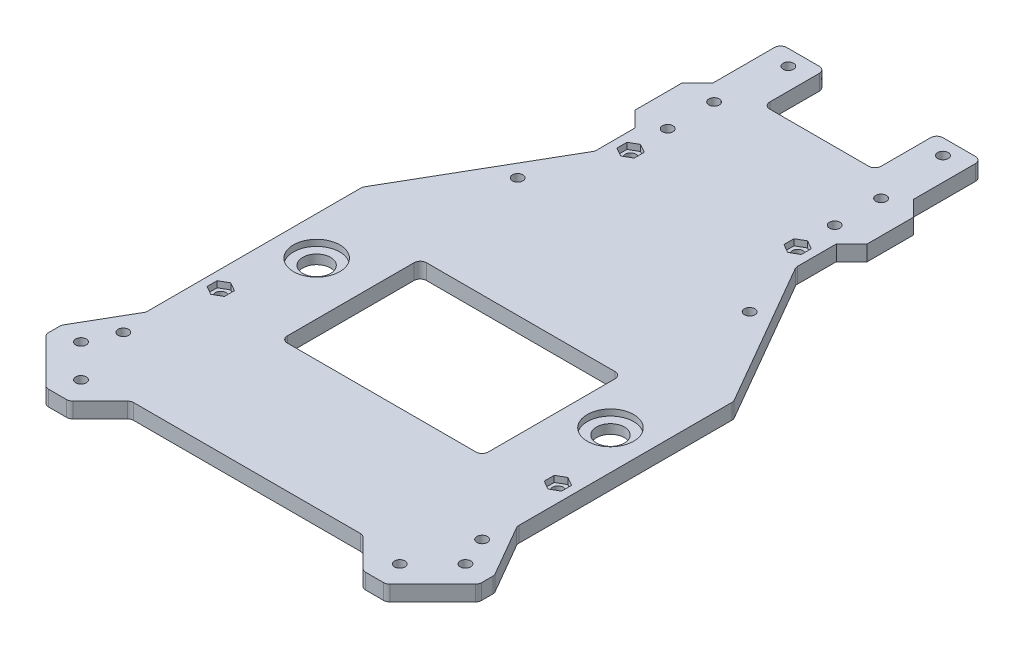
SolidWorks part; units mm, degrees
material "ABS PC"
ref_plane "Front Plane" through (0, 0, 0) normal (0, 0, 1) x (1, 0, 0)
ref_plane "Top Plane" through (0, 0, 0) normal (0, 1, 0) x (1, 0, 0)
ref_plane "Right Plane" through (0, 0, 0) normal (1, 0, 0) x (0, 0, -1)
sketch "Sketch1" plane through (0, 0, 0) normal (0, 1, 0) x (1, 0, 0)
  line L1 (70, -110) -> (-70, -110)
  line L2 (70, -110) -> (70, 110)
  line L3 (70, 110) -> (-70, 110)
  line L4 (-70, -110) -> (-70, 110)
  line L5 (70, -110) -> (-70, 110) construction
  line L6 (70, 110) -> (-70, -110) construction
  point P0 (0, 0)
  dimension "D1" = 220
  dimension "D2" = 140
extrude "Boss-Extrude1" add sketch "Sketch1" along normal blind 5
sketch "Sketch8" plane through (0, 5, 0) normal (0, 1, 0) x (1, 0, 0)
  line L0 (-70, 110) -> (-32.5, 110)
  line L1 (70, 110) -> (-70, 110) construction
  line L2 (-32.5, 110) -> (-32.5, 44.9519)
  line L3 (-32.5, 44.9519) -> (-70, -20)
  line L4 (-70, 110) -> (-70, -110) construction
  line L5 (-70, 110) -> (-70, -20)
  line L6 (0, 110) -> (0, -110) construction
  line L7 (-70, -110) -> (70, -110) construction
  line L8 (70, 110) -> (70, -20)
  line L9 (32.5, 44.9519) -> (70, -20)
  line L10 (32.5, 110) -> (32.5, 44.9519)
  line L11 (70, 110) -> (32.5, 110)
  dimension "D1" = 130
  dimension "D2" = 30
  dimension "D3" = 65
extrude "Cut-Extrude1" cut sketch "Sketch8" against normal blind 5
chamfer "Chamfer3" distance 15 angle 45 2 edges at (70, 2.5, 110) (-70, 2.5, 110)
sketch "Sketch10" plane through (0, 0, 0) normal (0, 1, 0) x (1, 0, 0)
  line L0 (0, 110) -> (0, -110) construction
  line L1 (32.5, 110) -> (-32.5, 110) construction
  line L2 (-55, -110) -> (55, -110) construction
  line L3 (-27, 78) -> (-27, 63) construction
  line L4 (-62.5, -102.5) -> (-56.8431, -96.8431) construction
  line L5 (-62.1464, -91.5398) -> (-51.5398, -102.1464) construction
  line L6 (-70, -95) -> (-55, -110) construction
  point P9 (27, 63)
  point P10 (27, 78)
  point P17 (51.5398, -102.1464)
  point P18 (62.1464, -91.5398)
  dimension "D1" = 15
  dimension "D2" = 27
  dimension "D3" = 32
  dimension "D4" = 15
  dimension "D5" = 8
sketch "Sketch15" plane through (0, 5, 0) normal (0, 1, 0) x (1, 0, 0)
  line L0 (0, 110) -> (0, -110) construction
  line L1 (32.5, 110) -> (-32.5, 110) construction
  line L2 (-55, -110) -> (55, -110) construction
  line L3 (25, 100) -> (-25, 100) construction
  line L4 (37.5, 25) -> (-37.5, 25) construction
  line L5 (58, -57) -> (-58, -57) construction
  point P9 (0, 100)
  point P13 (0, 25)
  point P15 (0, -57)
  dimension "D1" = 50
  dimension "D2" = 10
  dimension "D3" = 75
  dimension "D4" = 85
  dimension "D5" = 116
  dimension "D6" = 167
hole_wizard "CSK for M3 Flat Head Machine Screw3" positions "Sketch16" profile "Sketch17" countersink size "M3" standard "ANSI Metric"
sketch "Sketch16" plane through (0, 0, 0) normal (0, 1, 0) x (1, 0, 0)
  point P6 (37.5, 25)
  point P9 (-37.5, 25)
  point P12 (-25, 100)
  point P15 (25, 100)
sketch "Sketch17" plane through (37.5, 0, -25) normal (1, 0, 0) x (0, 0, -1)
  line L0 (0, 0) -> (0, 6.0215)
  line L1 (0, 6.0215) -> (1.7, 5)
  line L2 (1.7, 5) -> (1.7, 1.45)
  line L3 (1.7, 1.45) -> (3.15, 0)
  line L5 (3.15, 0) -> (0, 0)
  line L6 (-1.7, 1.45) -> (-3.15, 0) construction
  line L10 (0, 6.0215) -> (-1.7, 5) construction
  line L11 (0, -6.35) -> (0, 107.95) construction
  dimension "Hole Dia." = 3.4
  dimension "Hole Depth" = 5
  dimension "Near C'Sink Dia." = 6.3
  dimension "Near C'Sink Angle" = 90
  dimension "Drill Angle" = 118
sketch "Sketch18" plane through (0, 5, 0) normal (0, 1, 0) x (1, 0, 0)
  line L0 (32.5, 110) -> (-32.5, 110) construction
  line L1 (-46.4338, 114.6286) -> (34.8035, 114.6286)
  line L2 (-46.4338, 114.6286) -> (-46.4338, 105)
  line L3 (-46.4338, 105) -> (34.8035, 105)
  line L4 (34.8035, 114.6286) -> (34.8035, 105)
  dimension "D1" = 5
extrude "Cut-Extrude2" cut sketch "Sketch18" against normal blind 5
sketch "Sketch34" plane through (0, 5, 0) normal (0, 1, 0) x (1, 0, 0)
  line L0 (-70, -20) -> (-60, -2.6795)
  line L1 (-70, -20) -> (-32.5, 44.9519) construction
  line L2 (-60, -2.6795) -> (-60, -72.6795)
  line L3 (-60, -72.6795) -> (-70, -90)
  line L4 (-70, -20) -> (-70, -95) construction
  line L5 (-70, -90) -> (-70, -20)
  line L6 (0, -90.4055) -> (0, -61.6307) construction
  line L7 (70, -90) -> (70, -20)
  line L8 (60, -72.6795) -> (70, -90)
  line L9 (60, -2.6795) -> (60, -72.6795)
  line L10 (70, -20) -> (60, -2.6795)
  line L11 (-55, -110) -> (55, -110) construction
  dimension "D1" = 120
  dimension "D2" = 20
extrude "Cut-Extrude8" cut sketch "Sketch34" against normal blind 10
chamfer "Chamfer4" [suppressed] distance 20 angle 30
sketch "Sketch35" plane through (0, 5, 0) normal (0, 1, 0) x (1, 0, 0)
  line L1 (-30.5, -58.5) -> (34.5, -58.5)
  line L2 (-30.5, -58.5) -> (-30.5, -13.5)
  line L3 (-30.5, -13.5) -> (34.5, -13.5)
  line L4 (34.5, -58.5) -> (34.5, -13.5)
  line L5 (-30.5, -58.5) -> (34.5, -13.5) construction
  line L6 (-30.5, -13.5) -> (34.5, -58.5) construction
  point P0 (2, -36)
  dimension "D1" = 2
  dimension "D2" = 65
  dimension "D3" = 45
  dimension "D4" = 36
extrude "Cut-Extrude9" cut sketch "Sketch35" against normal through all
fillet "Fillet1" radius 2 4 edges at (-30.5, 2.5, 58.5) (-30.5, 2.5, 13.5) (34.5, 2.5, 13.5) (34.5, 2.5, 58.5)
sketch "Sketch36" plane through (0, 5, 0) normal (0, 1, 0) x (1, 0, 0)
  line L0 (0, -110) -> (0, -100) construction
  line L1 (-55, -110) -> (55, -110) construction
  line L2 (-47.5, -110) -> (-37.5, -100)
  line L3 (-37.5, -100) -> (37.5, -100)
  line L4 (-47.5, -110) -> (47.5, -110)
  line L6 (-70, -95) -> (-55, -110) construction
  line L7 (47.5, -110) -> (37.5, -100)
  dimension "D1" = 10
  dimension "D2" = 95
extrude "Cut-Extrude10" cut sketch "Sketch36" against normal through all
sketch "Sketch38" plane through (0, 0, 0) normal (0, -1, 0) x (1, 0, 0)
  line L0 (0, -105) -> (0, -90) construction
  line L1 (-32.5, -105) -> (32.5, -105) construction
  line L2 (18, -85) -> (-18, -85)
  line L3 (-18, -85) -> (-18, -105)
  line L4 (-18, -105) -> (18, -105)
  line L5 (18, -85) -> (18, -105)
  dimension "D1" = 90
  dimension "D2" = 20
  dimension "D3" = 36
extrude "Cut-Extrude14" cut sketch "Sketch38" against normal through all
sketch "Sketch39" plane through (0, 0, 0) normal (0, -1, 0) x (1, 0, 0)
  line L0 (0, 37.973) -> (0, 15.9654) construction
  circle A0 centre (-47.5, 30) radius 4.5
  circle A1 centre (47.5, 30) radius 4.5
  dimension "D1" = 95
  dimension "D2" = 9
  dimension "D3" = 30
extrude "Cut-Extrude15" cut sketch "Sketch39" against normal through all
hole_wizard "CSK for M3 Flat Head Machine Screw2" positions "Sketch40" profile "Sketch41" countersink size "M3" standard "ANSI Metric"
sketch "Sketch40" plane through (0, 0, 0) normal (0, -1, 0) x (-1, 0, 0)
  point P0 (-58, -82)
  point P3 (58, -82)
sketch "Sketch41" plane through (58, 0, 82) normal (1, 0, 0) x (0, 0, -1)
  line L0 (0, 0) -> (0, 11.0215)
  line L1 (0, 11.0215) -> (1.7, 10)
  line L2 (1.7, 10) -> (1.7, 1.45)
  line L3 (1.7, 1.45) -> (3.15, 0)
  line L5 (3.15, 0) -> (0, 0)
  line L6 (-1.7, 1.45) -> (-3.15, 0) construction
  line L10 (0, 11.0215) -> (-1.7, 10) construction
  line L11 (0, -6.35) -> (0, 107.95) construction
  dimension "Hole Dia." = 3.4
  dimension "Hole Depth" = 10
  dimension "Near C'Sink Dia." = 6.3
  dimension "Near C'Sink Angle" = 90
  dimension "Drill Angle" = 118
hole_wizard "Ø3.5 (3.5) Diameter Hole1" positions "Sketch45" profile "Sketch46" hole size "Ø3.5" standard "ANSI Metric"
sketch "Sketch45" plane through (0, 5, 0) normal (0, 1, 0) x (1, 0, 0)
  line L0 (-32.5, 44.9519) -> (-32.5, 105) construction
  line L1 (-60, -72.6795) -> (-60, -2.6795) construction
  line L2 (-32.5, 105) -> (-18, 105) construction
  point P0 (-54.5, -54)
  point P2 (-27, 51)
  dimension "D1" = 5.5
  dimension "D2" = 5.5
  dimension "D3" = 54
  dimension "D4" = 105
sketch "Sketch46" plane through (-54.5, 5, 54) normal (1, 0, 0) x (0, 0, 1)
  line L0 (0, 0) -> (0, 6.0515)
  line L1 (0, 6.0515) -> (1.75, 5)
  line L2 (1.75, 5) -> (1.75, 0)
  line L5 (1.75, 0) -> (0, 0)
  line L10 (0, 6.0515) -> (-1.75, 5) construction
  line L11 (0, -6.35) -> (0, 107.95) construction
  dimension "Hole Dia." = 3.5
  dimension "Hole Depth" = 5
  dimension "Drill Angle" = 118
mirror "Mirror1" about plane through (0, 0, 0) normal (1, 0, 0) of "Ø3.5 (3.5) Diameter Hole1"
sketch "Sketch47" plane through (0, 5, 0) normal (0, 1, 0) x (1, 0, 0)
  line L0 (0, 13.2168) -> (0, -3.9151) construction
  line L1 (29.8, 49.3834) -> (29.8, 52.6166)
  line L2 (29.8, 52.6166) -> (27, 54.2332)
  line L3 (27, 54.2332) -> (24.2, 52.6166)
  line L4 (24.2, 52.6166) -> (24.2, 49.3834)
  line L5 (24.2, 49.3834) -> (27, 47.7668)
  line L6 (27, 47.7668) -> (29.8, 49.3834)
  line L7 (57.3, -55.6166) -> (57.3, -52.3834)
  line L8 (57.3, -52.3834) -> (54.5, -50.7668)
  line L9 (54.5, -50.7668) -> (51.7, -52.3834)
  line L10 (51.7, -52.3834) -> (51.7, -55.6166)
  line L11 (51.7, -55.6166) -> (54.5, -57.2332)
  line L12 (54.5, -57.2332) -> (57.3, -55.6166)
  line L13 (-54.5, -57.2332) -> (-57.3, -55.6166)
  line L14 (-51.7, -55.6166) -> (-54.5, -57.2332)
  line L15 (-51.7, -52.3834) -> (-51.7, -55.6166)
  line L16 (-54.5, -50.7668) -> (-51.7, -52.3834)
  line L17 (-57.3, -52.3834) -> (-54.5, -50.7668)
  line L18 (-57.3, -55.6166) -> (-57.3, -52.3834)
  line L19 (-27, 47.7668) -> (-29.8, 49.3834)
  line L20 (-24.2, 49.3834) -> (-27, 47.7668)
  line L21 (-24.2, 52.6166) -> (-24.2, 49.3834)
  line L22 (-27, 54.2332) -> (-24.2, 52.6166)
  line L23 (-29.8, 52.6166) -> (-27, 54.2332)
  line L24 (-29.8, 49.3834) -> (-29.8, 52.6166)
  circle A0 centre (27, 51) radius 2.8 construction
  circle A1 centre (54.5, -54) radius 2.8 construction
  circle A2 centre (-54.5, -54) radius 2.8 construction
  circle A3 centre (-27, 51) radius 2.8 construction
  dimension "D1" = 5.6
extrude "Cut-Extrude16" cut sketch "Sketch47" against normal blind 2
hole_wizard "CSK for M3 Flat Head Machine Screw1" positions "Sketch52" profile "Sketch53" countersink size "M3" standard "ANSI Metric"
sketch "Sketch52" plane through (0, 0, 0) normal (0, -1, 0) x (-1, 0, 0)
  point P0 (27, 63)
  point P3 (27, 78)
  point P6 (-27, 78)
  point P9 (-27, 63)
  point P12 (62.1464, -91.5398)
  point P15 (51.5398, -102.1464)
  point P18 (-51.5398, -102.1464)
  point P21 (-62.1464, -91.5398)
sketch "Sketch53" plane through (-27, 0, -63) normal (1, 0, 0) x (0, 0, -1)
  line L0 (0, 0) -> (0, 6.0215)
  line L1 (0, 6.0215) -> (1.7, 5)
  line L2 (1.7, 5) -> (1.7, 1.45)
  line L3 (1.7, 1.45) -> (3.15, 0)
  line L5 (3.15, 0) -> (0, 0)
  line L6 (-1.7, 1.45) -> (-3.15, 0) construction
  line L10 (0, 6.0215) -> (-1.7, 5) construction
  line L11 (0, -6.35) -> (0, 107.95) construction
  dimension "Hole Dia." = 3.4
  dimension "Hole Depth" = 5
  dimension "Near C'Sink Dia." = 6.3
  dimension "Near C'Sink Angle" = 90
  dimension "Drill Angle" = 118
sketch "Sketch48" plane through (0, 5, 0) normal (0, 1, 0) x (1, 0, 0)
  line L0 (27, 78) -> (27, 63) construction
  line L1 (27, 70.5) -> (37.5, 70.5) construction
  line L2 (32.5, 58) -> (32.5, 83)
  line L3 (32.5, 105) -> (32.5, 44.9519) construction
  line L4 (32.5, 83) -> (37.5, 78)
  line L5 (37.5, 78) -> (37.5, 63)
  line L6 (32.5, 58) -> (37.5, 63)
  line L7 (0, 71.0199) -> (0, 60.9015) construction
  line L8 (-32.5, 58) -> (-37.5, 63)
  line L9 (-37.5, 78) -> (-37.5, 63)
  line L10 (-32.5, 83) -> (-37.5, 78)
  line L11 (-32.5, 58) -> (-32.5, 83)
  point P13 (32.5, 70.5)
  point P16 (-32.5, 70.5)
  dimension "D1" = 45
  dimension "D2" = 5
  dimension "D3" = 25
extrude "Boss-Extrude4" add sketch "Sketch48" against normal up to surface (5 mm away) up to face at (-27, 0, -81.15)
fillet "Fillet3" radius 2 22 edges at (-32.5, 2.5, -105) (-32.5, 2.5, -44.9519) (-60, 2.5, 2.6795) (-60, 2.5, 72.6795) (-70, 2.5, 90) (-70, 2.5, 95) (-55, 2.5, 110) (-47.5, 2.5, 110) (-37.5, 2.5, 100) (37.5, 2.5, 100) (47.5, 2.5, 110) (55, 2.5, 110) (70, 2.5, 95) (70, 2.5, 90) (60, 2.5, 72.6795) (60, 2.5, 2.6795) (32.5, 2.5, -44.9519) (18, 2.5, -105) (18, 2.5, -85) (-18, 2.5, -85) (-18, 2.5, -105) (32.5, 2.5, -105)
sketch "Sketch54" plane through (0, 5, 0) normal (0, 1, 0) x (1, 0, 0)
  line L0 (0, -24.4413) -> (0, -37.1235) construction
  circle A0 centre (-47.5, -30) radius 7.5
  circle A1 centre (-47.5, -30) radius 4.5
  circle A2 centre (-47.5, -30) radius 4.5 construction
  circle A3 centre (47.5, -30) radius 4.5
  circle A4 centre (47.5, -30) radius 7.5
  dimension "D1" = 15
extrude "Cut-Extrude17" cut sketch "Sketch54" against normal blind 2
